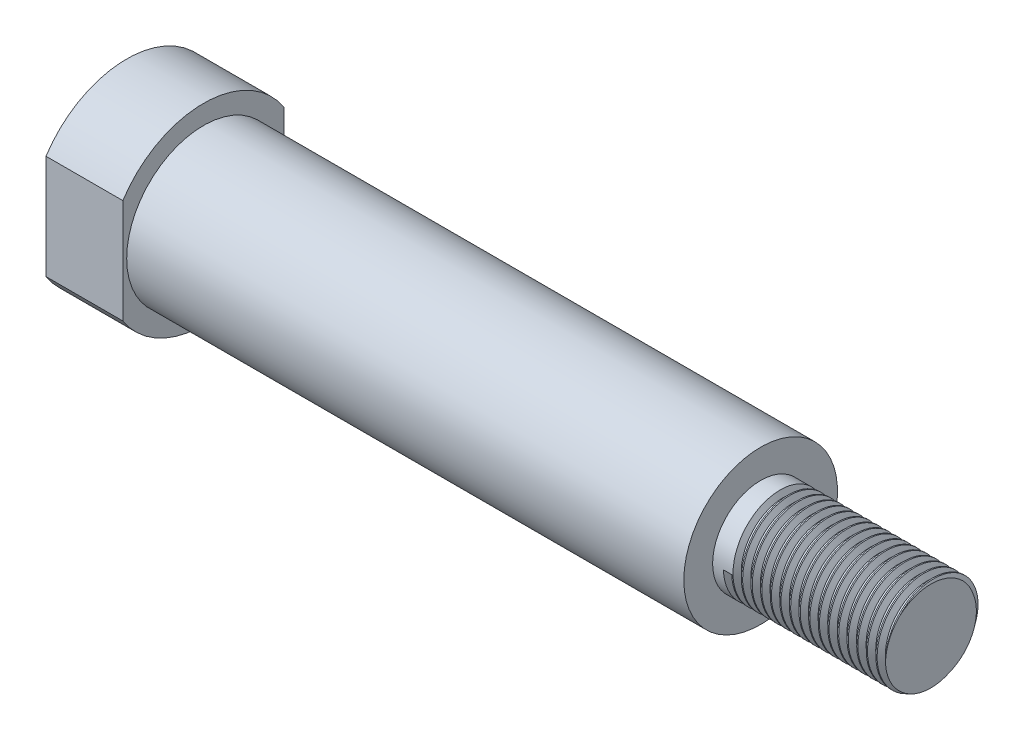
SolidWorks part; units mm, degrees
ref_plane "Front Plane" through (0, 0, 0) normal (0, 0, 1) x (1, 0, 0)
ref_plane "Top Plane" through (0, 0, 0) normal (0, 1, 0) x (1, 0, 0)
ref_plane "Right Plane" through (0, 0, 0) normal (1, 0, 0) x (0, 0, -1)
sketch "Sketch1" plane through (0, 0, 0) normal (1, 0, 0) x (0, 0, -1)
  line L0 (4.2, 2.7129) -> (4.2, -2.7129)
  line L2 (-4.2, 2.7129) -> (-4.2, -2.7129)
  arc A0 (-4.2, -2.7129) -> (4.2, -2.7129) centre (0, 0) ccw
  arc A1 (4.2, 2.7129) -> (-4.2, 2.7129) centre (0, 0) ccw
  dimension "D1" = 10
  dimension "D2" = 4.2
  dimension "D3" = 4.2
extrude "Boss-Extrude1" add sketch "Sketch1" along normal blind 4
sketch "Sketch2" plane through (4, 0, 0) normal (1, 0, 0) x (0, 0, -1)
  circle A0 centre (0, 0) radius 4
  dimension "D1" = 8
extrude "Boss-Extrude2" add sketch "Sketch2" along normal blind 29
sketch "Sketch3" plane through (33, 0, 0) normal (1, 0, 0) x (0, 0, -1)
  circle A0 centre (0, 0) radius 2.5
  dimension "D1" = 5
extrude "Boss-Extrude3" add sketch "Sketch3" along normal blind 9
sketch "Sketch6" plane through (42, 0, 0) normal (1, 0, 0) x (0, 0, -1)
  circle A0 centre (0, 0) radius 2.5 construction
  circle A1 centre (0, 0) radius 2.5
thread "Thread1" pitch 0.5 method cut trim with start face yes profile "Thread Profile2" start angle 0, offset 1, length 9, pitch 0.5, diameter 5
ref_plane "Plane2" through (43, 0, 2.5) normal (0, -1, 0) x (0, 0, 1)
sketch "Thread Profile2" plane through (43, 0, 2.5) normal (0, -1, 0) x (0, 0, 1)
  line L0 (0, 0) -> (0, 0.5) construction
  line L11 (0, 0) -> (0, 0.4375)
  line L12 (0, 0.4375) -> (-0.2706, 0.2812)
  line L13 (-0.2706, 0.2812) -> (-0.2706, 0.1562)
  line L15 (-0.2706, 0.1562) -> (0, 0)
  line L17 (-0.2706, 0.2187) -> (0, 0.2187) construction
  point P2 (0, 0)
  dimension "Pitch" = 0.5
  dimension "Profile_Angle" = 60
  dimension "Profile_Land" = 0.125
  dimension "Profile_Height" = 0.2706
